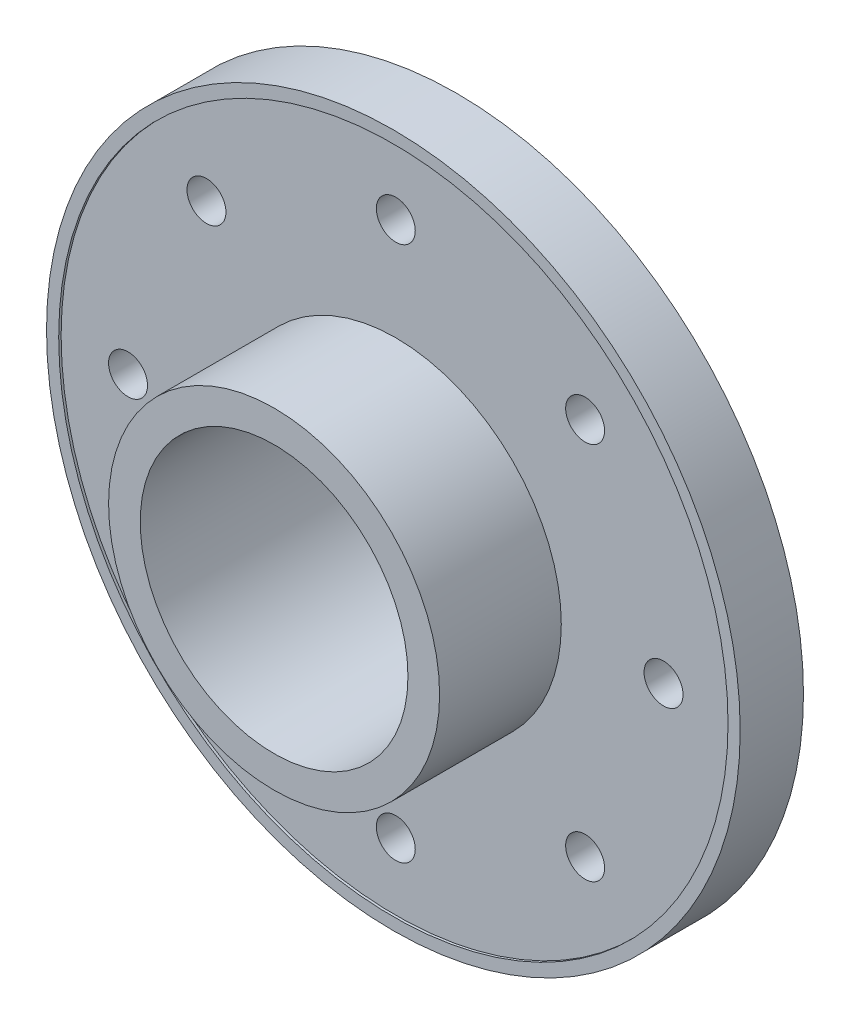
SolidWorks part; units mm, degrees
ref_plane "Front Plane" through (0, 0, 0) normal (0, 0, 1) x (1, 0, 0)
ref_plane "Top Plane" through (0, 0, 0) normal (0, 1, 0) x (1, 0, 0)
ref_plane "Right Plane" through (0, 0, 0) normal (1, 0, 0) x (0, 0, -1)
other "Configuration Table"
sketch "草图1" plane through (0, 0, 0) normal (0, 0, 1) x (1, 0, 0)
  circle A0 centre (0, 0) radius 27.5
extrude "凸台-拉伸1" add sketch "草图1" along normal blind 4 contours A0
sketch "草图2" plane through (0, 0, 0) normal (0, 0, -1) x (-1, 0, 0)
  circle A0 centre (0, 0) radius 11.1
extrude "切除-拉伸1" cut sketch "草图2" against normal blind 4 contours A0
sketch "草图3" plane through (0, 0, 4) normal (0, 0, 1) x (1, 0, 0)
  circle A0 centre (0, 0) radius 11.1
  circle A1 centre (0, 0) radius 13.6
  circle M3 centre (0, 0) radius 11.1
extrude "凸台-拉伸3" add sketch "草图3" along normal blind 20 contours A1 M3 | A0 region at (-13.2153, 0, 4)
sketch "草图6" plane through (0, 0, 4) normal (0, 0, -1) x (-1, 0, 0)
  circle A0 centre (0, 0) radius 11
extrude "切除-拉伸3" cut sketch "草图6" against normal blind 20 contours A0
sketch "草图7" plane through (0, 0, 0) normal (0, 0, -1) x (-1, 0, 0)
  circle A0 centre (22, 0) radius 1.6
  circle A1 centre (-22, 0) radius 1.6
  circle A6 centre (-14.7522, 16.2848) radius 1.6
  circle A7 centre (0, 22) radius 1.6
  circle A8 centre (16.2848, 14.7522) radius 1.6
  circle A9 centre (14.7522, -16.2848) radius 1.6
  circle A10 centre (-15.5563, -15.5563) radius 1.6
  circle A11 centre (0, -22) radius 1.6
extrude "切除-拉伸4" cut sketch "草图7" against normal blind 20 contours A1 | A0 | A8
sketch "草图8" plane through (0, 0, 0) normal (0, 0, -1) x (-1, 0, 0)
  line L3 (22, -14.7733) -> (22.8302, -15.3308)
  line L5 (22, 14.7733) -> (22.8302, 15.3308)
  arc A2 (22, -14.7733) -> (22, 14.7733) centre (0, 0) ccw
  arc A4 (22.8302, -15.3308) -> (22.8292, 15.3322) centre (0, 0) ccw
  circle M13 centre (0, 0) radius 27.5
extrude "凸台-拉伸4" add sketch "草图8" along normal blind 10 contours A2 L3 L5 M13 region at (-26.8115, 0, 0)
sketch "草图10" plane through (0, 0, 0) normal (1, 0, 0) x (0, 0, -1)
  line L0 (0, 15.3308) -> (2.5, 15.3308)
  line L1 (10, 15.3308) -> (0, 15.3308) construction
  line L2 (2.5, 15.3308) -> (10, 0)
  line L3 (10, 15.3308) -> (10, -15.3308) construction
  line L4 (10, 0) -> (2.5, -15.3308)
  line L5 (10, -15.3308) -> (0, -15.3308) construction
  line L6 (2.5, -15.3308) -> (10, -15.3308)
  line L7 (10, -15.3308) -> (10, 0)
  line L8 (10, 15.3308) -> (10, 0)
  line L9 (2.5, 15.3308) -> (10, 15.3308)
extrude "切除-拉伸5" cut sketch "草图10" against normal blind 100 contours L2 | L4 region at (0, 10.2205, -7.5) region at (0, -10.2205, -7.5)
sketch "草图11" plane through (0, 0, 0) normal (0, 0, -1) x (-1, 0, 0)
  circle A0 centre (0, 0) radius 11.1
  circle A1 centre (0, 0) radius 11
extrude "凸台-拉伸6" add sketch "草图11" against normal blind 4 contours A1 | A0 region at (0, 0, 0)
sketch "草图12" plane through (0, 0, 0) normal (0, 0, -1) x (-1, 0, 0)
  circle A1 centre (16.2848, 14.7522) radius 2.8007
  circle A2 centre (22, 0) radius 3.3735
  circle A3 centre (-22, 0) radius 2.3641
extrude "凸台-拉伸7" add sketch "草图12" against normal blind 4
sketch "草图13" plane through (0, 0, 0) normal (0, 0, -1) x (-1, 0, 0)
  circle A0 centre (0, 22) radius 1.6
  circle A1 centre (15.5563, 15.5563) radius 1.6
  circle A2 centre (22, 0) radius 1.6
  circle A3 centre (15.5563, -15.5563) radius 1.6
  circle A4 centre (0, -22) radius 1.6
  circle A5 centre (-15.5563, -15.5563) radius 1.6
  circle A6 centre (-22, 0) radius 1.6
  circle A7 centre (-15.5563, 15.5563) radius 1.6
extrude "切除-拉伸6" cut sketch "草图13" against normal blind 4
sketch "草图14" plane through (0, 0, 0) normal (0, 0, -1) x (-1, 0, 0)
  line L0 (0, 0) -> (0, 15.7731)
  line L1 (0, 15.7731) -> (1.7666, 15.7731)
  line L2 (1.7666, 15.7731) -> (1.7666, -16.755)
  line L3 (1.7666, -16.755) -> (0, -16.755)
  line L4 (0, -16.755) -> (0, 0)
extrude "凸台-拉伸8" add sketch "草图14" along normal blind 10 contours L4 L0 L1 L2 L3
sketch "草图15" plane through (0, 0, 0) normal (1, 0, 0) x (0, 0, -1)
  line L0 (10, 15.7731) -> (10, -16.755)
  line L1 (10, -16.755) -> (0, -16.755)
  line L2 (0, -16.755) -> (0, 15.7731)
  line L3 (0, 15.7731) -> (10, 15.7731)
extrude "切除-拉伸7" cut sketch "草图15" against normal blind 50 contours L3 L0 L1 L2
sketch "草图16" plane through (0, 0, 0) normal (0, 0, -1) x (-1, 0, 0)
  line L1 (22.8, -12.4964) -> (24.1154, -13.2173)
  line L4 (22.8, 12.4964) -> (24.1154, 13.2173)
  arc A3 (24.1154, -13.2173) -> (24.1154, 13.2173) centre (0, 0) ccw
  arc A4 (22.8, 12.4964) -> (22.8, -12.4964) centre (0, 0) cw
  circle M5 centre (0, 0) radius 27.5
extrude "凸台-拉伸9" add sketch "草图16" along normal blind 10 contours L4 A4 L1 M5 region at (-26.2685, 0, 0)
sketch "草图18" plane through (0, 0, 0) normal (1, 0, 0) x (0, 0, -1)
  line L0 (0, 13.2173) -> (2.5, 13.2173)
  line L1 (10, 13.2173) -> (0, 13.2173) construction
  line L2 (2.5, 13.2173) -> (10, 0)
  line L3 (10, 13.2173) -> (10, -13.2173) construction
  line L4 (10, 0) -> (2.5, -13.2173)
  line L5 (10, -13.2173) -> (0, -13.2173) construction
  line L6 (2.5, -13.2173) -> (10, -13.2173)
  line L7 (10, -13.2173) -> (10, 0)
  line L8 (2.5, 13.2173) -> (10, 13.2173)
  line L9 (10, 13.2173) -> (10, 0)
extrude "切除-拉伸8" cut sketch "草图18" against normal blind 50 contours L2 | L4 region at (0, 8.8116, -7.5) region at (0, -8.8116, -7.5)
sketch "草图19" plane through (0, 0, 4) normal (0, 0, 1) x (1, 0, 0)
  circle A0 centre (0, 0) radius 13.6
  circle A1 centre (0, 0) radius 27.5
extrude "切除-拉伸9" cut sketch "草图19" against normal blind 1 contours A1 | A0
sketch "草图20" plane through (0, 0, 0) normal (0, 0, -1) x (-1, 0, 0)
  circle A1 centre (16.1679, 6.697) radius 2.7
  circle A2 centre (-13.8837, 10.6533) radius 2.7
  circle A3 centre (-2.2842, -17.3503) radius 2.7
extrude "切除-拉伸10" cut sketch "草图20" against normal blind 3 contours A2 | A1 | A3 | A3 region at (-16.1679, 6.697, 0) region at (13.8837, 10.6533, 0) region at (2.2842, -17.3503, 0)
sketch "草图21" plane through (0, 0, 24) normal (0, 0, 1) x (1, 0, 0)
  circle A0 centre (0, 0) radius 11
  circle A1 centre (0, 0) radius 13.6
extrude "切除-拉伸11" cut sketch "草图21" against normal blind 11
sketch "草图22" plane through (0, 0, 13) normal (0, 0, 1) x (1, 0, 0)
  circle A0 centre (0, 0) radius 11
  circle A1 centre (0, 0) radius 13.6
  circle M3 centre (0, 0) radius 11
extrude "凸台-拉伸12" add sketch "草图22" against normal blind 23 contours M3 | A1 region at (0, 0, 13)
sketch "草图23" plane through (0, 0, 3) normal (0, 0, 1) x (1, 0, 0)
  circle A0 centre (-16.1679, 6.697) radius 2.7
  circle A1 centre (13.8837, 10.6533) radius 2.7
  circle A2 centre (2.2842, -17.3503) radius 2.7
extrude "凸台-拉伸13" add sketch "草图23" against normal blind 3
sketch "草图25" plane through (0, 0, 0) normal (0, 0, -1) x (-1, 0, 0)
  circle A0 centre (0, 0) radius 27.5
  circle A1 centre (0, 0) radius 13.6
  circle A2 centre (0, 22) radius 1.6
  circle A3 centre (-15.5563, 15.5563) radius 1.6
  circle A4 centre (-22, 0) radius 1.6
  circle A5 centre (-15.5563, -15.5563) radius 1.6
  circle A6 centre (0, -22) radius 1.6
  circle A7 centre (15.5563, -15.5563) radius 1.6
  circle A8 centre (22, 0) radius 1.6
  circle A9 centre (15.5563, 15.5563) radius 1.6
extrude "凸台-拉伸14" add sketch "草图25" along normal blind 2
sketch "草图26" plane through (0, 0, 3) normal (0, 0, 1) x (1, 0, 0)
  circle A0 centre (0, 0) radius 27.5
  circle A1 centre (0, 0) radius 28.5
  circle M3 centre (0, 0) radius 13.6
  circle M4 centre (0, 0) radius 27.5
  circle M5 centre (0, 22) radius 1.6
  circle M6 centre (-15.5563, 15.5563) radius 1.6
  circle M7 centre (-22, 0) radius 1.6
  circle M8 centre (-15.5563, -15.5563) radius 1.6
  circle M9 centre (0, -22) radius 1.6
  circle M10 centre (15.5563, -15.5563) radius 1.6
  circle M11 centre (22, 0) radius 1.6
  circle M12 centre (15.5563, 15.5563) radius 1.6
extrude "凸台-拉伸15" add sketch "草图26" against normal blind 5 contours M4 M6 M8 M10 M12 M11 M9 M7 M5 M3 | M3 | A1 region at (-26.7222, 0, 3) region at (0, 0, 3)
sketch "草图28" plane through (0, 0, 3) normal (0, 0, 1) x (1, 0, 0)
  circle A0 centre (0, 0) radius 28.5
  circle A1 centre (0, 0) radius 27.5
  circle M3 centre (0, 0) radius 13.6
  circle M4 centre (0, 22) radius 1.6
  circle M5 centre (-15.5563, 15.5563) radius 1.6
  circle M6 centre (-22, 0) radius 1.6
  circle M7 centre (-15.5563, -15.5563) radius 1.6
  circle M8 centre (0, -22) radius 1.6
  circle M9 centre (15.5563, -15.5563) radius 1.6
  circle M10 centre (22, 0) radius 1.6
  circle M11 centre (15.5563, 15.5563) radius 1.6
extrude "凸台-拉伸16" add sketch "草图28" along normal blind 0.2 contours A1 M3 M5 M7 M9 M11 M10 M8 M6 M4 | M3 | A0 region at (-26.7222, 0, 3) region at (0, 0, 3)
